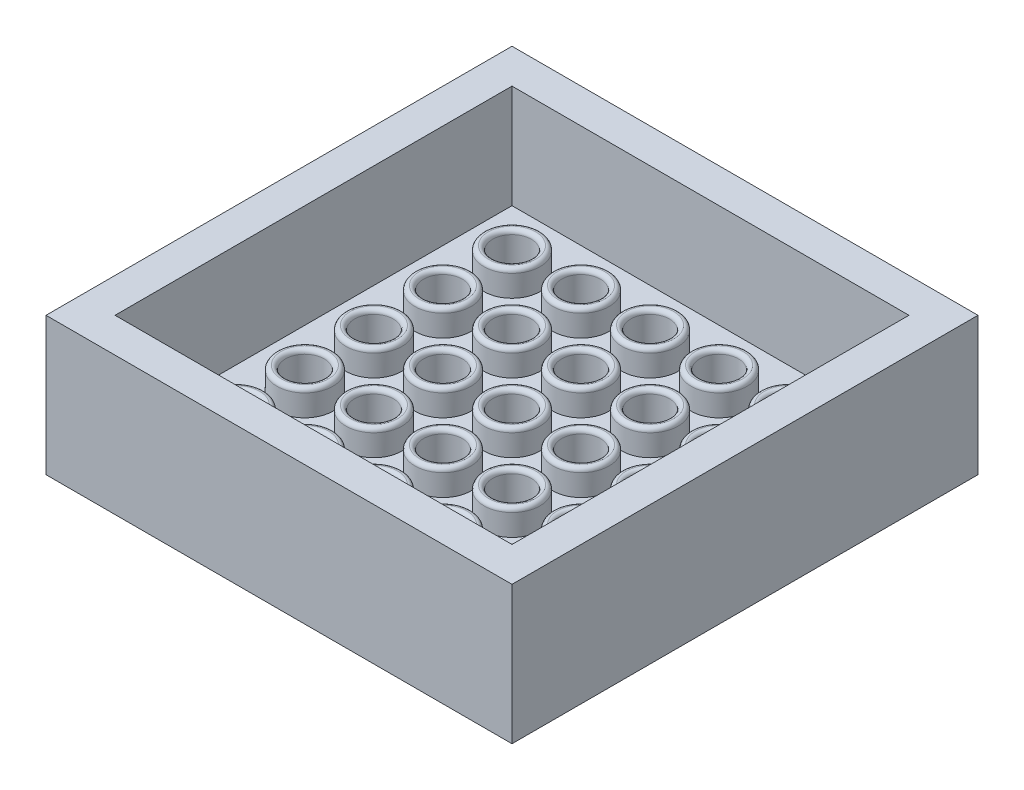
SolidWorks part; units mm, degrees
ref_plane "Front Plane" through (0, 0, 0) normal (0, 0, 1) x (1, 0, 0)
ref_plane "Top Plane" through (0, 0, 0) normal (0, 1, 0) x (1, 0, 0)
ref_plane "Right Plane" through (0, 0, 0) normal (1, 0, 0) x (0, 0, -1)
sketch "Sketch1" plane through (0, 0, 0) normal (0, 1, 0) x (1, 0, 0)
  line L0 (-13.5, 13.5) -> (13.5, 13.5)
  line L1 (-11.5, -11.5) -> (11.5, -11.5)
  line L2 (-11.5, -11.5) -> (-11.5, 11.5)
  line L3 (-11.5, 11.5) -> (11.5, 11.5)
  line L4 (11.5, -11.5) -> (11.5, 11.5)
  line L5 (-11.5, -11.5) -> (11.5, 11.5) construction
  line L6 (-11.5, 11.5) -> (11.5, -11.5) construction
  line L7 (13.5, -13.5) -> (13.5, 13.5)
  line L8 (-13.5, -13.5) -> (13.5, -13.5)
  line L9 (-13.5, -13.5) -> (-13.5, 13.5)
  point P0 (0, 0)
  dimension "D1" = 23
  dimension "D2" = 2
extrude "Boss-Extrude1" add sketch "Sketch1" along normal blind 2
sketch "Sketch2" plane through (0, 0, 0) normal (0, -1, 0) x (1, 0, 0)
  line L1 (-13.5, 13.5) -> (13.5, 13.5)
  line L2 (-13.5, 13.5) -> (-13.5, -13.5)
  line L3 (-13.5, -13.5) -> (13.5, -13.5)
  line L4 (13.5, 13.5) -> (13.5, -13.5)
  line L5 (-13.5, 13.5) -> (13.5, -13.5) construction
  line L6 (-13.5, -13.5) -> (13.5, 13.5) construction
  point P0 (0, 0)
extrude "Boss-Extrude2" add sketch "Sketch2" along normal blind 2
sketch "Sketch3" plane through (0, -2, 0) normal (0, -1, 0) x (1, 0, 0)
  line L0 (-11.5, 11.5) -> (11.5, 11.5)
  line L1 (-13.5, -13.5) -> (13.5, -13.5)
  line L2 (-13.5, -13.5) -> (-13.5, 13.5)
  line L3 (-13.5, 13.5) -> (13.5, 13.5)
  line L4 (13.5, -13.5) -> (13.5, 13.5)
  line L5 (-13.5, -13.5) -> (13.5, 13.5) construction
  line L6 (-13.5, 13.5) -> (13.5, -13.5) construction
  line L7 (11.5, -11.5) -> (11.5, 11.5)
  line L8 (-11.5, -11.5) -> (11.5, -11.5)
  line L9 (-11.5, -11.5) -> (-11.5, 11.5)
  point P0 (0, 0)
  dimension "D1" = 2
extrude "Boss-Extrude3" add sketch "Sketch3" along normal blind 3
sketch "Sketch6" plane through (0, 0, 0) normal (0, 1, 0) x (1, 0, 0)
  line L0 (11.5, -11.5) -> (11.5, 11.5) construction
  line L1 (11.5, 11.5) -> (-11.5, 11.5) construction
  circle A0 centre (8, 8) radius 1.625
  dimension "D2" = 3.25
  dimension "D1" = 3.5
  dimension "D3" = 3.5
extrude "Boss-Extrude5" add sketch "Sketch6" along normal blind 1.5
sketch "Sketch7" plane through (0, 1.5, 0) normal (0, 1, 0) x (1, 0, 0)
  circle A0 centre (8, 8) radius 1.125
  circle A1 centre (8, 8) radius 1.625 construction
  dimension "D1" = 0.5
extrude "Cut-Extrude2" cut sketch "Sketch7" against normal up to next
fillet "Fillet1" radius 0.25 2 edges at (8, 1.5, -6.375) (8, 1.5, -6.875)
pattern_linear "LPattern3" count 5 spacing 4 along (0, 0, 1) count 5 spacing 4 along (-1, 0, 0) of "Boss-Extrude5", "Cut-Extrude2", "Fillet1"
sketch "Sketch11" plane through (0, -2, 0) normal (0, -1, 0) x (1, 0, 0)
  line L0 (11.5, 11.5) -> (-11.5, 11.5) construction
  line L1 (-11.5, 11.5) -> (-11.5, -11.5) construction
  circle A0 centre (-9.9, 9.9) radius 0.75
  dimension "D1" = 1.5
  dimension "D3" = 1.6
  dimension "D2" = 1.6
extrude "Boss-Extrude8" add sketch "Sketch11" along normal up to surface (3 mm away) up to face at (0, -5, 0)
pattern_linear "LPattern2" count 6 spacing 4 along (1, 0, 0) count 6 spacing 4 along (0, 0, -1) of "Boss-Extrude8"
ref_plane "Plane1" through (0, -3.5, 0) normal (0, -1, 0) x (-1, 0, 0)
sketch "Sketch14" plane through (0, -3.5, 0) normal (0, -1, 0) x (-1, 0, 0)
  circle A0 centre (0, 0) radius 2.9698
extrude "Boss-Extrude10" add sketch "Sketch14" against normal blind 0.5
sketch "Sketch8" plane through (0, -5, 0) normal (0, -1, 0) x (1, 0, 0)
  line L1 (-13.5, -13.5) -> (13.5, -13.5)
  line L2 (-13.5, -13.5) -> (-13.5, 13.5)
  line L3 (-13.5, 13.5) -> (13.5, 13.5)
  line L4 (13.5, -13.5) -> (13.5, 13.5)
  line L5 (-13.5, -13.5) -> (13.5, 13.5) construction
  line L6 (-13.5, 13.5) -> (13.5, -13.5) construction
  point P0 (0, 0)
extrude "Boss-Extrude6" add sketch "Sketch8" along normal blind 2
sketch "Sketch9" plane through (0, -7, 0) normal (0, -1, 0) x (1, 0, 0)
  circle A0 centre (0, 0) radius 4.25
  dimension "D1" = 8.5
extrude "Cut-Extrude3" cut sketch "Sketch9" against normal blind 3
sketch "Sketch10" plane through (0, 2, 0) normal (0, 1, 0) x (1, 0, 0)
  line L3 (11.5, -11.5) -> (-11.5, -11.5)
  line L4 (11.5, -11.5) -> (11.5, 11.5)
  line L5 (11.5, 11.5) -> (-11.5, 11.5)
  line L6 (-11.5, -11.5) -> (-11.5, 11.5)
  line L7 (11.5, -11.5) -> (-11.5, 11.5) construction
  line L8 (11.5, 11.5) -> (-11.5, -11.5) construction
  line L9 (13.5, -13.5) -> (-13.5, -13.5)
  line L10 (13.5, -13.5) -> (13.5, 13.5)
  line L11 (13.5, 13.5) -> (-13.5, 13.5)
  line L12 (-13.5, -13.5) -> (-13.5, 13.5)
  line L13 (13.5, -13.5) -> (-13.5, 13.5) construction
  line L14 (13.5, 13.5) -> (-13.5, -13.5) construction
  point P0 (0, 0)
  point P5 (0, 0)
extrude "Boss-Extrude7" add sketch "Sketch10" along normal blind 4
sketch "Sketch15" plane through (0, -4, 0) normal (0, -1, 0) x (1, 0, 0)
  circle A0 centre (2.1, 1.9) radius 0.75
  circle A1 centre (-1.9, -2.1) radius 0.75
  circle A2 centre (2.1, -2.1) radius 0.75
  circle A3 centre (-1.9, 1.9) radius 0.75
extrude "Boss-Extrude11" add sketch "Sketch15" along normal up to surface (3 mm away) up to face at (0, -7, -4.25)
sketch "Sketch17" plane through (0, -7, 0) normal (0, -1, 0) x (1, 0, 0)
  line L1 (13.5, -13.5) -> (-13.5, -13.5)
  line L2 (13.5, -13.5) -> (13.5, 13.5)
  line L3 (13.5, 13.5) -> (-13.5, 13.5)
  line L4 (-13.5, -13.5) -> (-13.5, 13.5)
  line L5 (13.5, -13.5) -> (-13.5, 13.5) construction
  line L6 (13.5, 13.5) -> (-13.5, -13.5) construction
  point P0 (0, 0)
extrude "Cut-Extrude4" cut sketch "Sketch17" against normal up to surface (5 mm away) up to face at (10.1, -2, -6.85)
equation "\"D3@Sketch6\"=\"D1@Sketch6\""
equation "\"D3@Sketch11\"=\"D2@Sketch11\""
